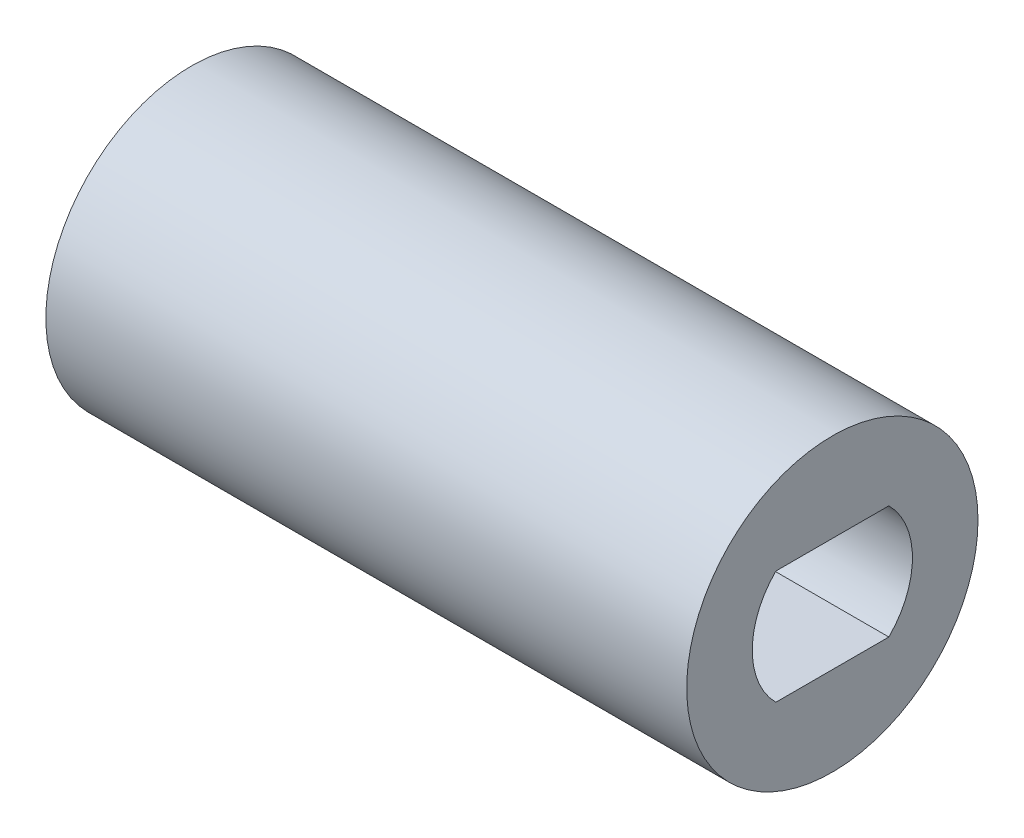
SolidWorks part; units mm, degrees
ref_plane "Front Plane" through (0, 0, 0) normal (0, 0, 1) x (1, 0, 0)
ref_plane "Top Plane" through (0, 0, 0) normal (0, 1, 0) x (1, 0, 0)
ref_plane "Right Plane" through (0, 0, 0) normal (1, 0, 0) x (0, 0, -1)
sketch "Sketch1" plane through (0, 0, 0) normal (1, 0, 0) x (0, 0, -1)
  circle A0 centre (0, 0) radius 20
  dimension "D1" = 40
extrude "Boss-Extrude1" add sketch "Sketch1" along normal blind 10
sketch "Sketch2" plane through (10, 0, 0) normal (1, 0, 0) x (0, 0, -1)
  line L0 (-2.0906, 19.8904) -> (-1.2245, 21.3904)
  line L1 (-1.2245, 21.3904) -> (1.2245, 21.3904)
  line L2 (1.2245, 21.3904) -> (2.0906, 19.8904)
  line L3 (2.0906, 19.8904) -> (-2.0906, 19.8904)
  line L4 (-2.0906, 19.8904) -> (0, 0) construction
  line L5 (0, 0) -> (2.0906, 19.8904) construction
  circle A0 centre (0, 0) radius 20 construction
  point P4 (0, 19.8904)
  dimension "D1" = 60
  dimension "D2" = 60
  dimension "D4" = 1.5
  dimension "D3" = 12
extrude "Boss-Extrude2" add sketch "Sketch2" against normal blind 6
chamfer "Chamfer1" distance 1.6 angle 45 2 edges at (10, 21.3904, 0) (4, 21.3904, 0)
pattern_circular "CirPattern1" count 15 over 360 about axis through (10, 0, 0) along (1, 0, 0) of "Boss-Extrude2", "Chamfer1"
sketch "Sketch4" plane through (0, 0, 0) normal (-1, 0, 0) x (0, 0, 1)
  line L0 (0, 20) -> (0, 0) construction
  line L1 (0, 0) -> (-4.1582, 19.563) construction
  line L6 (-6.1803, 19.0211) -> (-2.0906, 19.8904)
  line L7 (-2.0906, 19.8904) -> (-3.2495, 21.1776)
  line L8 (-3.2495, 21.1776) -> (-5.6451, 20.6684)
  line L9 (-5.6451, 20.6684) -> (-6.1803, 19.0211)
  line L10 (-6.1803, 19.0211) -> (0, 0) construction
  line L11 (0, 0) -> (-2.0906, 19.8904) construction
  circle A1 centre (0, 0) radius 20 construction
  point P2 (0, 20)
  point P13 (-4.1355, 19.4558)
  dimension "D2" = 60
  dimension "D1" = 12
  dimension "D3" = 60
  dimension "D4" = 12
  dimension "D5" = 1.5
extrude "Boss-Extrude3" add sketch "Sketch4" against normal blind 6
chamfer "Chamfer2" distance 1.6 angle 45 2 edges at (6, 20.923, -4.4473) (0, 20.923, -4.4473)
pattern_circular "CirPattern2" count 15 over 360 about axis through (0, 0, 0) along (1, 0, 0) of "Boss-Extrude3", "Chamfer2"
sketch "Sketch5" plane through (10, 0, 0) normal (1, 0, 0) x (0, 0, -1)
  circle A0 centre (0, 0) radius 5
  dimension "D1" = 10
extrude "Boss-Extrude4" add sketch "Sketch5" along normal blind 12
sketch "Sketch6" plane through (22, 0, 0) normal (1, 0, 0) x (0, 0, -1)
  line L0 (-1.9391, 1.95) -> (1.9391, 1.95)
  line L1 (1.9391, -1.95) -> (-1.9391, -1.95)
  circle A0 centre (0, 0) radius 2.75
  dimension "D1" = 5.5
  dimension "D2" = 3.9
extrude "Cut-Extrude1" cut sketch "Sketch6" against normal blind 8 contours L0 A0 L1 region at (22, 0, 0)
fillet "Fillet1" radius 10 1 edges at (10, 0, -5)
sketch "Sketch7" plane through (22, 0, 0) normal (1, 0, 0) x (0, 0, -1)
  circle A0 centre (0, 0) radius 5 construction
  circle A1 centre (0, 0) radius 5
  circle A2 centre (0, 0) radius 25
  dimension "D1" = 50
extrude "Cut-Extrude2" cut sketch "Sketch7" against normal through all both and the other way through all
equation "\"D2@Sketch2\"=\"D1@Sketch2\""
equation "\"D3@Sketch4\"=\"D2@Sketch4\""
equation "\"Num Treads\" = 15"
equation "\"D1@CirPattern1\"=\"Num Treads\""
equation "\"D1@CirPattern2\"=\"Num Treads\""
